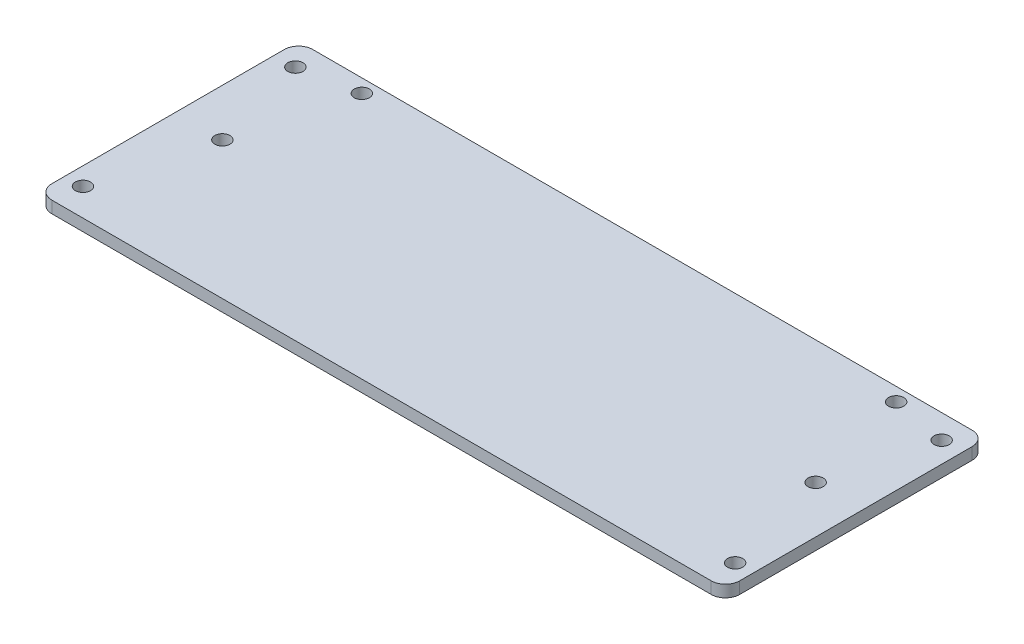
SolidWorks part; units mm, degrees
ref_plane "Front Plane" through (0, 0, 0) normal (0, 0, 1) x (1, 0, 0)
ref_plane "Top Plane" through (0, 0, 0) normal (0, 1, 0) x (1, 0, 0)
ref_plane "Right Plane" through (0, 0, 0) normal (1, 0, 0) x (0, 0, -1)
sketch "Sketch1" plane through (0, 0, 0) normal (0, 1, 0) x (1, 0, 0)
  line L0 (0, 0) -> (0, -69.85)
  line L1 (0, -69.85) -> (184.15, -69.85)
  line L2 (184.15, -69.85) -> (184.15, 0)
  line L3 (184.15, 0) -> (0, 0)
  point P2 (0, -69.85)
  point P5 (125.4198, -69.85)
  dimension "D1" = 184.15
  dimension "D3" = 69.85
extrude "Boss-Extrude1" add sketch "Sketch1" along normal blind 3.175 contours L2 L3 L0 L1 region at (92.075, 0, 34.925)
fillet "Fillet1" radius 3.81 4 edges at (184.15, 1.5875, 0) (184.15, 1.5875, 69.85) (0, 1.5875, 0) (0, 1.5875, 69.85)
sketch "Sketch2" plane through (0, 3.175, 0) normal (0, 1, 0) x (1, 0, 0)
  line L0 (92.075, 0) -> (92.075, -69.85) construction
  line L1 (180.34, 0) -> (3.81, 0) construction
  line L2 (3.81, -69.85) -> (180.34, -69.85) construction
  circle A4 centre (4.7743, -62.4896) radius 2.032 construction
  circle A5 centre (4.7743, -62.4896) radius 2.032
  circle A6 centre (12.6631, -33.0482) radius 2.032 construction
  circle A7 centre (20.5519, -3.6068) radius 2.032 construction
  circle A8 centre (5.5645, -6.4101) radius 2.032 construction
  circle A9 centre (12.6631, -33.0482) radius 2.032
  circle A10 centre (20.5519, -3.6068) radius 2.032
  circle A11 centre (5.5645, -6.4101) radius 2.032
  circle A12 centre (179.3757, -62.4896) radius 2.032
  circle A13 centre (171.4869, -33.0482) radius 2.032
  circle A14 centre (178.5855, -6.4101) radius 2.032
  circle A15 centre (163.5981, -3.6068) radius 2.032
extrude "Cut-Extrude1" cut sketch "Sketch2" against normal through all contours A11 | A9 | A5 | A12 | A13 | A15 | A14 | A10 region at (4.7743, 3.175, 62.4896) region at (12.6631, 3.175, 33.0482) region at (5.5645, 3.175, 6.4101) region at (179.3757, 3.175, 62.4896) region at (171.4869, 3.175, 33.0482) region at (178.5855, 3.175, 6.4101) region at (163.5981, 3.175, 3.6068)
